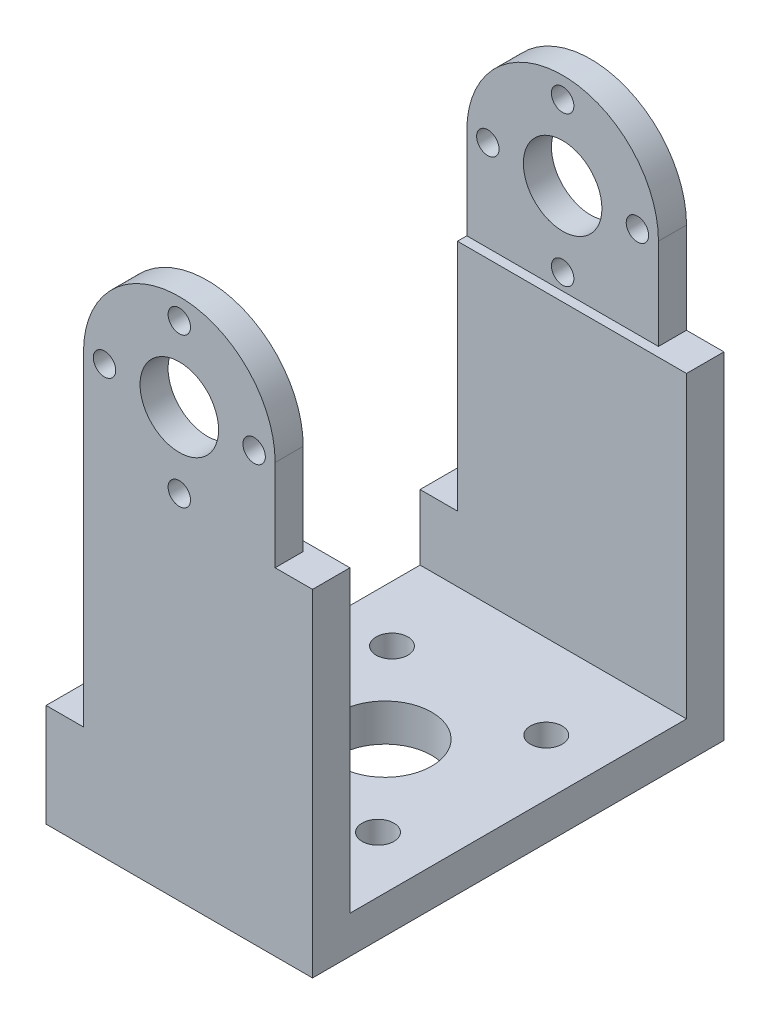
SolidWorks part; units mm, degrees
ref_plane "Front Plane" through (0, 0, 0) normal (0, 0, 1) x (1, 0, 0)
ref_plane "Top Plane" through (0, 0, 0) normal (0, 1, 0) x (1, 0, 0)
ref_plane "Right Plane" through (0, 0, 0) normal (1, 0, 0) x (0, 0, -1)
sketch "Sketch1" plane through (0, 0, 0) normal (0, 0, 1) x (1, 0, 0)
  line L0 (0, 0) -> (0, -100) construction
  line L1 (0, -100) -> (-70, -100) construction
  line L2 (-10.25, -60) -> (-70, -60) construction
  line L4 (-10.25, 0) -> (10.25, 0)
  line L5 (-10.25, 0) -> (-10.25, -60)
  line L7 (10.25, 0) -> (10.25, -60)
  line L8 (-10.25, 0) -> (10.25, 0)
  line L9 (-10.25, 0) -> (-10.25, -100)
  line L10 (-10.25, -100) -> (10.25, -100)
  line L11 (10.25, 0) -> (10.25, -100)
  circle A0 centre (0, 0) radius 10.25
  circle A1 centre (0, 0) radius 8
  circle A2 centre (0, 0) radius 4.2
  circle A3 centre (0, 8) radius 1.2
  circle A4 centre (8, 0) radius 1.2
  circle A5 centre (0, -8) radius 1.2
  circle A6 centre (-8, 0) radius 1.2
  point P16 (0, 0)
  dimension "D1" = 20.5
  dimension "D2" = 16
  dimension "D3" = 8.4
  dimension "D4" = 2.4
  dimension "D6" = 100
  dimension "D7" = 70
  dimension "D8" = 40
  dimension "D5" = 4
extrude "Boss-Extrude1" add sketch "Sketch1" along normal blind 22 and the other way blind 22 contours A0 L5 L7 | A6 L4 A0 A4 A1 A5 | A6 A1 A5 A4 L4 A2 | A6 L4 A2 A4 A1 A3 | A6 A1 A3 A4 L4 A0 region at (8.972, 1.0478, 0) region at (9.725, -0.2292, 0) region at (6.9906, -0.9364, 0) region at (5.5, 0.1769, 0) region at (0, -53.9967, 0)
sketch "Sketch2" plane through (-10.25, 0, 0) normal (-1, 0, 0) x (0, 0, 1)
  line L0 (22, 10.25) -> (-22, 10.25) construction
  line L1 (-19, 10.25) -> (19, 10.25)
  line L2 (-19, 10.25) -> (-19, -9.75)
  line L3 (-19, -9.75) -> (19, -9.75)
  line L4 (19, 10.25) -> (19, -9.75)
  line L5 (22, 0) -> (22, 10.25) construction
  line L6 (-22, 10.25) -> (-22, 0) construction
  dimension "D1" = 3
  dimension "D2" = 3
  dimension "D3" = 20
extrude "Cut-Extrude1" cut sketch "Sketch2" against normal through all
sketch "Sketch3" plane through (0, -9.75, 0) normal (0, 1, 0) x (1, 0, 0)
  line L1 (-10.25, 22) -> (-17.25, 22)
  line L2 (-10.25, 22) -> (-10.25, -22)
  line L3 (-10.25, -22) -> (-17.25, -22)
  line L4 (-17.25, 22) -> (-17.25, -22)
  line L5 (10.25, 22) -> (17.25, 22)
  line L6 (10.25, 22) -> (10.25, -22)
  line L7 (10.25, -22) -> (17.25, -22)
  line L8 (17.25, 22) -> (17.25, -22)
  dimension "D1" = 7
  dimension "D2" = 7
extrude "Boss-Extrude2" add sketch "Sketch3" against normal blind 36
sketch "Sketch5" plane through (-17.25, 0, 0) normal (-1, 0, 0) x (0, 0, 1)
  line L0 (-22, -9.75) -> (22, -9.75) construction
  line L1 (-17, -9.75) -> (17, -9.75)
  line L2 (-17, -9.75) -> (-17, -59.75)
  line L3 (-17, -59.75) -> (17, -59.75)
  line L4 (17, -9.75) -> (17, -59.75)
  line L8 (-19, 0) -> (-19, -9.75) construction
  dimension "D1" = 34
  dimension "D2" = 2
  dimension "D3" = 50
extrude "Cut-Extrude3" cut sketch "Sketch5" against normal through all
sketch "Sketch6" plane through (0, 0, 22) normal (0, 0, 1) x (1, 0, 0)
  line L1 (10.25, -45.75) -> (-10.25, -45.75)
  line L2 (10.25, -45.75) -> (10.25, -100)
  line L3 (10.25, -100) -> (-10.25, -100)
  line L4 (-10.25, -45.75) -> (-10.25, -100)
extrude "Cut-Extrude4" cut sketch "Sketch6" against normal through all
sketch "Sketch20" plane through (0, -45.75, 0) normal (0, -1, 0) x (1, 0, 0)
  line L1 (-17.25, 22) -> (17.25, 22)
  line L2 (-17.25, 22) -> (-17.25, -22)
  line L3 (-17.25, -22) -> (17.25, -22)
  line L4 (17.25, 22) -> (17.25, -22)
  line L5 (-17.25, 17) -> (17.25, 17) construction
  line L6 (17.25, -17) -> (-17.25, -17) construction
  line L8 (-14.25, 17) -> (14.25, 17)
  line L9 (-14.25, 17) -> (-14.25, -17)
  line L10 (-14.25, -17) -> (14.25, -17)
  line L11 (14.25, 17) -> (14.25, -17)
  circle A0 centre (0, 0) radius 5
  circle A2 centre (-8.25, 9) radius 1.7
  circle A3 centre (8.25, 9) radius 1.7
  circle A4 centre (8.25, -9) radius 1.7
  circle A5 centre (-8.25, -9) radius 1.7
  line M7 (-17.25, 17) -> (17.25, 17)
  dimension "D1" = 3
  dimension "D2" = 3
  dimension "D3" = 6
  dimension "D4" = 8
  dimension "D5" = 2
  dimension "D6" = 2
extrude "Boss-Extrude5" add sketch "Sketch20" against normal blind 4 contours L11 L9 L10 A5 A4 A3 A2 A0 M7 region at (0, -45.75, 16.5564)
sketch "Sketch21" plane through (0, 0, -22) normal (0, 0, -1) x (-1, 0, 0)
  line L0 (-17.25, -45.75) -> (17.25, -45.75) construction
  line L1 (-17.25, -9.75) -> (-14.25, -9.75)
  line L2 (-17.25, -9.75) -> (-17.25, -45.75)
  line L3 (-17.25, -45.75) -> (-14.25, -45.75)
  line L4 (-14.25, -9.75) -> (-14.25, -45.75)
  line L6 (17.25, -9.75) -> (14.25, -9.75)
  line L7 (17.25, -9.75) -> (17.25, -45.75)
  line L8 (17.25, -45.75) -> (14.25, -45.75)
  line L9 (14.25, -9.75) -> (14.25, -45.75)
  dimension "D1" = 3
  dimension "D2" = 3
extrude "Cut-Extrude12" cut sketch "Sketch21" against normal through all
sketch "Sketch22" plane through (0, 0, -22) normal (0, 0, -1) x (-1, 0, 0)
  line L0 (-14.25, -45.75) -> (-14.25, -9.75) construction
  line L1 (-10.25, -9.75) -> (-14.25, -9.75)
  line L2 (-10.25, -9.75) -> (-10.25, -34.75)
  line L3 (-10.25, -34.75) -> (-14.25, -34.75)
  line L4 (-14.25, -9.75) -> (-14.25, -34.75)
  line L5 (14.25, -9.75) -> (14.25, -45.75) construction
  line L6 (10.25, -9.75) -> (14.25, -9.75)
  line L7 (10.25, -9.75) -> (10.25, -34.75)
  line L8 (10.25, -34.75) -> (14.25, -34.75)
  line L9 (14.25, -9.75) -> (14.25, -34.75)
  dimension "D1" = 25
extrude "Cut-Extrude14" cut sketch "Sketch22" against normal through all contours L9 L8 L7 L6
sketch "Sketch23" plane through (-10.25, 0, 0) normal (-1, 0, 0) x (0, 0, 1)
  line L0 (19, -9.75) -> (17, -9.75) construction
  line L1 (18, -9.75) -> (-18, -9.75)
  line L2 (18, -9.75) -> (18, -41.75)
  line L3 (18, -41.75) -> (-18, -41.75)
  line L4 (-18, -9.75) -> (-18, -41.75)
  line L6 (-19, 0) -> (-19, -9.75) construction
  line L7 (19, -9.75) -> (19, 0) construction
  dimension "D1" = 1
  dimension "D2" = 1
extrude "Cut-Extrude15" cut sketch "Sketch23" against normal through all both and the other way through all
